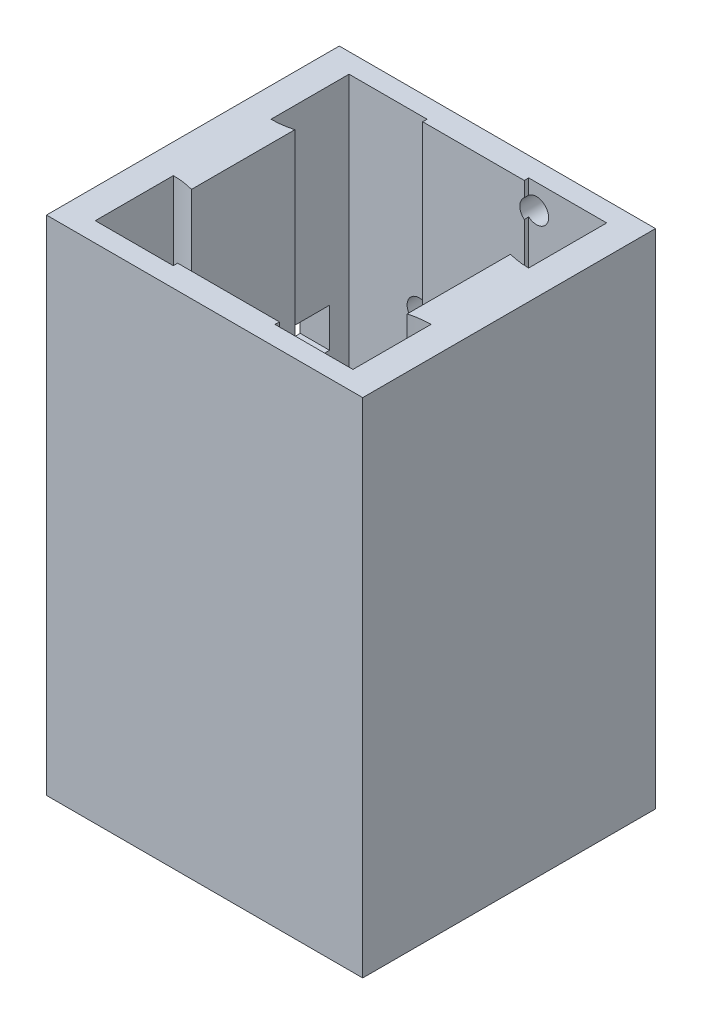
SolidWorks part; units mm, degrees
ref_plane "Front Plane" through (0, 0, 0) normal (0, 0, 1) x (1, 0, 0)
ref_plane "Top Plane" through (0, 0, 0) normal (0, 1, 0) x (1, 0, 0)
ref_plane "Right Plane" through (0, 0, 0) normal (1, 0, 0) x (0, 0, -1)
sketch "Sketch1" plane through (0, 0, 0) normal (0, 1, 0) x (1, 0, 0)
  line L0 (16.2, 0) -> (16.2, -30) construction
  line L1 (0, 0) -> (32.4, 0)
  line L2 (0, 0) -> (0, -30)
  line L3 (0, -30) -> (32.4, -30)
  line L4 (32.4, 0) -> (32.4, -30)
  line L5 (0, -15) -> (32.4, -15) construction
  circle A0 centre (6.2, -5) radius 1.75
  circle A1 centre (26.2, -5) radius 1.75
  circle A2 centre (26.2, -25) radius 1.75
  circle A3 centre (6.2, -25) radius 1.75
  dimension "D3" = 3.5
  dimension "D8" = 20
  dimension "D1" = 30
  dimension "D2" = 32.4
  dimension "D6" = 10
  dimension "D7" = 10
  dimension "D9" = 20
  dimension "D4" = 2
  dimension "D5" = 2
extrude "Boss-Extrude1" add sketch "Sketch1" along normal blind 25
sketch "Sketch2" plane through (0, 25, 0) normal (0, 1, 0) x (1, 0, 0)
  line L1 (16.2, 0) -> (16.2, -30) construction
  line L2 (32.4, 0) -> (0, 0) construction
  line L3 (0, -30) -> (32.4, -30) construction
  line L4 (0, -15) -> (32.4, -15) construction
  line L5 (0, 0) -> (0, -30) construction
  line L6 (32.4, -30) -> (32.4, 0) construction
  circle A0 centre (16.2, -15) radius 4
  point P14 (18.7071, -16.8704)
  dimension "D1" = 8
extrude "Cut-Extrude1" cut sketch "Sketch2" against normal blind 20
sketch "Sketch3" plane through (0, 25, 0) normal (0, 1, 0) x (1, 0, 0)
  line L0 (3, -10) -> (3, -20)
  line L1 (0, 0) -> (32.4, 0)
  line L2 (0, 0) -> (0, -30)
  line L3 (0, -30) -> (32.4, -30)
  line L4 (32.4, 0) -> (32.4, -30)
  line L5 (3, -2) -> (29.4, -2)
  line L6 (3, -2) -> (3, -28)
  line L7 (3, -28) -> (29.4, -28)
  line L8 (29.4, -2) -> (29.4, -28)
  line L9 (11, -28) -> (21.4, -28)
  line L10 (29.4, -20) -> (29.4, -10)
  line L11 (21.4, -2) -> (11, -2)
  arc A0 (11, -2) -> (3, -10) centre (3, -2) cw
  arc A1 (21.4, -28) -> (29.4, -20) centre (29.4, -28) cw
  arc A2 (29.4, -10) -> (21.4, -2) centre (29.4, -2) cw
  arc A3 (3, -20) -> (11, -28) centre (3, -28) cw
  circle M17 centre (16.2, -15) radius 4
  line M20 (0, 0) -> (0, -30)
  line M21 (0, -30) -> (32.4, -30)
  line M22 (32.4, -30) -> (32.4, 0)
  line M23 (32.4, 0) -> (0, 0)
  dimension "D5" = 8
  dimension "D6" = 8
  dimension "D7" = 8
  dimension "D8" = 8
  dimension "D1" = 3
  dimension "D2" = 3
  dimension "D3" = 2
  dimension "D4" = 2
extrude "Boss-Extrude2" add sketch "Sketch3" along normal blind 3 contours L5 L8 L7 L6 L0 M23 M20 M21 M22 | L0 A3 L7 A1 L8 A2 L5 A0 M17 region at (8.9189, 25, 7.9189) region at (16.2, 25, 0.4416)
sketch "Sketch4" plane through (0, 28, 0) normal (0, 1, 0) x (1, 0, 0)
  line L0 (16.2, 0) -> (16.2, -30) construction
  line L9 (32.4, 0) -> (0, 0) construction
  line L10 (0, -30) -> (32.4, -30) construction
  line L11 (32.4, -15) -> (0, -15) construction
  line L12 (5.15, -20.2943) -> (5.15, -9.7057)
  line L13 (0, 0) -> (0, -30) construction
  line L14 (32.4, -30) -> (32.4, 0) construction
  line L15 (29.4, -20) -> (29.4, -28) construction
  line L16 (21.4, -28) -> (29.4, -28) construction
  line L17 (3, -28) -> (11, -28) construction
  line L18 (3, -20) -> (3, -28) construction
  line L19 (3, -2) -> (11, -2) construction
  line L20 (21.4, -2) -> (29.4, -2) construction
  line L21 (29.4, -2) -> (29.4, -10) construction
  line L22 (3, -2) -> (3, -10) construction
  line L23 (0, -30) -> (32.4, -30)
  line L24 (0, 0) -> (0, -30)
  line L25 (32.4, 0) -> (0, 0)
  line L26 (32.4, -30) -> (32.4, 0)
  line L27 (29.4, -20) -> (29.4, -28)
  line L28 (21.4, -28) -> (29.4, -28)
  line L29 (3, -28) -> (11, -28)
  line L30 (3, -20) -> (3, -28)
  line L31 (3, -2) -> (11, -2)
  line L32 (21.4, -2) -> (29.4, -2)
  line L33 (29.4, -2) -> (29.4, -10)
  line L34 (3, -2) -> (3, -10)
  line L35 (10.9873, -2.45) -> (21.4127, -2.45)
  line L36 (27.25, -9.7057) -> (27.25, -20.2943)
  line L37 (10.9873, -27.55) -> (21.4127, -27.55)
  arc A0 (29.4, -20) -> (21.4, -28) centre (29.4, -28) ccw construction
  arc A1 (11, -28) -> (3, -20) centre (3, -28) ccw construction
  arc A2 (21.4, -2) -> (29.4, -10) centre (29.4, -2) ccw construction
  arc A3 (3, -10) -> (11, -2) centre (3, -2) ccw construction
  arc A4 (29.4, -20) -> (27.25, -20.2943) centre (29.4, -28) ccw
  arc A5 (11, -28) -> (10.9873, -27.55) centre (3, -28) ccw
  arc A6 (21.4, -2) -> (21.4127, -2.45) centre (29.4, -2) ccw
  arc A7 (3, -10) -> (5.15, -9.7057) centre (3, -2) ccw
  arc A8 (10.9873, -2.45) -> (11, -2) centre (3, -2) ccw
  arc A9 (5.15, -20.2943) -> (3, -20) centre (3, -28) ccw
  arc A10 (21.4127, -27.55) -> (21.4, -28) centre (29.4, -28) ccw
  arc A11 (27.25, -9.7057) -> (29.4, -10) centre (29.4, -2) ccw
  point P15 (16.2, -15)
  dimension "D1" = 22.1
  dimension "D2" = 11.05
  dimension "D3" = 25.1
  dimension "D4" = 12.55
extrude "Boss-Extrude3" add sketch "Sketch4" along normal blind 23.5
sketch "Sketch5" plane through (0, 0, 0) normal (0, 0, -1) x (-1, 0, 0)
  line L0 (-32.4, 28) -> (0, 28) construction
  line L1 (-32.4, 28) -> (0, 28)
  line L2 (-5.15, 28) -> (-5.15, 36.9803) construction
  line L3 (0, 51.5) -> (0, 0) construction
  line L4 (-27.25, 28) -> (-27.25, 39.4314) construction
  line L5 (-32.4, 51.5) -> (-32.4, 0) construction
  line L6 (-16.2, 28) -> (-16.2, 36.5707) construction
  circle A0 centre (-22.2, 49) radius 1.25
  circle A1 centre (-10.2, 34) radius 1.25
  dimension "D6" = 2.5
  dimension "D7" = 2.5
  dimension "D1" = 6
  dimension "D2" = 12
  dimension "D3" = 5.15
  dimension "D4" = 5.15
  dimension "D5" = 6
  dimension "D8" = 15
extrude "Cut-Extrude2" cut sketch "Sketch5" along direction (0, 0, 1) on the side against the normal up to surface (2.45 mm away) contours A0 | A1 region at (22.2, 49, 0) region at (10.2, 34, 0) up to face at (16.2, 39.75, 2.45)
sketch "Sketch6" plane through (0, 0, 0) normal (-1, 0, 0) x (0, 0, 1)
  line L0 (0, 28) -> (30, 28) construction
  line L1 (0, 28) -> (30, 28)
  line L2 (0, 51.5) -> (0, 0) construction
  line L3 (4, 28) -> (26, 28)
  line L4 (4, 28) -> (4, 32)
  line L5 (4, 32) -> (26, 32)
  line L6 (26, 28) -> (26, 32)
  line L7 (30, 51.5) -> (30, 0) construction
  dimension "D1" = 4
  dimension "D2" = 4
  dimension "D3" = 4
extrude "Cut-Extrude3" cut sketch "Sketch6" along direction (1, 0, 0) on the side against the normal up to surface (5.15 mm away) contours L1 L6 L5 L4 region at (0, 30, 15) up to face at (5.15, 39.75, 15)
